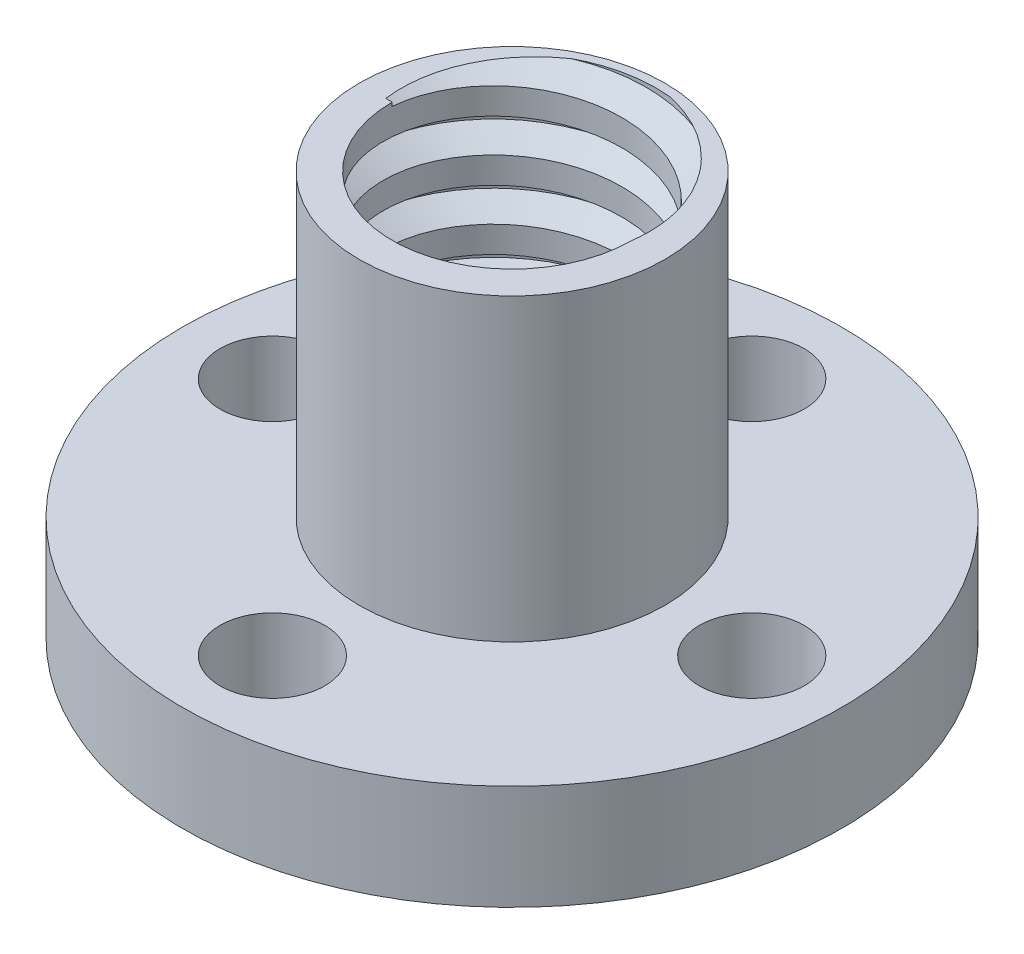
SolidWorks part; units mm, degrees
ref_plane "Plan de face" through (0, 0, 0) normal (0, 0, 1) x (1, 0, 0)
ref_plane "Plan de dessus" through (0, 0, 0) normal (0, 1, 0) x (1, 0, 0)
ref_plane "Plan de droite" through (0, 0, 0) normal (1, 0, 0) x (0, 0, -1)
sketch "Esquisse1" plane through (0, 0, 0) normal (0, 0, 1) x (1, 0, 0)
  line L0 (-4, 0) -> (-5.1, 0)
  line L1 (-5.1, 0) -> (-5.1, 1.5)
  line L2 (-5.1, 1.5) -> (-11, 1.5)
  line L3 (-11, 1.5) -> (-11, 5)
  line L4 (-11, 5) -> (-5.1, 5)
  line L5 (-5.1, 5) -> (-5.1, 15)
  line L6 (-5.1, 15) -> (-4, 15)
  line L7 (-4, 15) -> (-4, 0)
  line L8 (0, 0) -> (0, -11.1141) construction
  dimension "D1" = 4
  dimension "D2" = 5.1
  dimension "D3" = 11
  dimension "D4" = 1.5
  dimension "D5" = 3.5
  dimension "D6" = 10
revolve "Révolution1" add sketch "Esquisse1" angle 360 about L8
sketch "Esquisse2" plane through (0, 5, 0) normal (0, 1, 0) x (1, 0, 0)
  circle A1 centre (0, 8) radius 1.75
  circle A2 centre (8, 0) radius 1.75
  circle A3 centre (0, -8) radius 1.75
  circle A4 centre (-8, 0) radius 1.75
  point P13 (0, 0)
  dimension "D1" = 3.5
  dimension "D2" = 8
  dimension "D3" = 4
extrude "Enlèv. mat.-Extru.1" cut sketch "Esquisse2" against normal through all
thread "Filetage1" pitch 1.5 method cut trim with start face yes trim with end face yes profile "Profil de filetage1" start angle 0, offset 1, length 0, pitch 2, diameter 8
ref_plane "Plan1" through (-4, 16, 0) normal (0, 0, 1) x (-1, 0, 0)
sketch "Profil de filetage1" plane through (-4, 16, 0) normal (0, 0, 1) x (-1, 0, 0)
  line L0 (0, 0) -> (0, 1.5) construction
  line L1 (0, 0) -> (0.8119, 0.4687)
  line L2 (0.8119, 0.4687) -> (0.8119, 0.6562)
  line L3 (0.8119, 0.6562) -> (0, 1.125)
  line L4 (0.8119, 0.5625) -> (0, 0.5625) construction
  line L11 (0, 0) -> (0, 1.125)
  point P2 (0, 0)
  dimension "Pitch" = 1.5
  dimension "Profile_Angle" = 60
  dimension "Profile_Land" = 0.1875
  dimension "Profile_Height" = 0.8119
